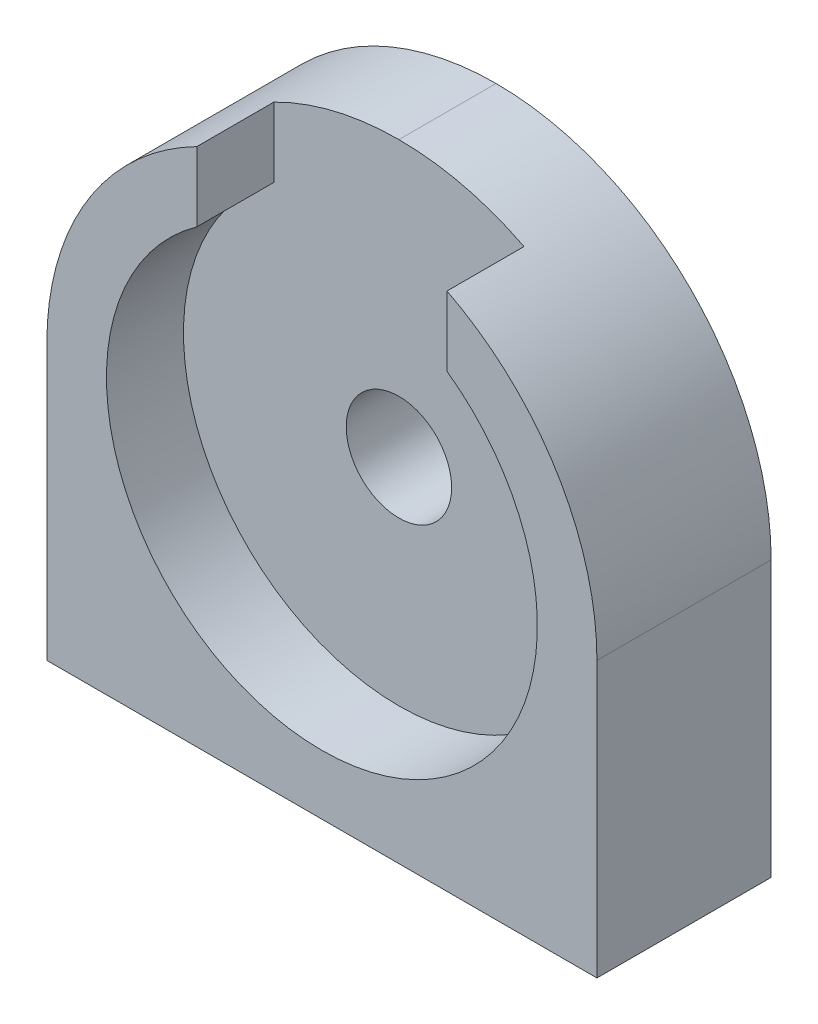
SolidWorks part; units mm, degrees
ref_plane "Front Plane" through (0, 0, 0) normal (0, 0, 1) x (1, 0, 0)
ref_plane "Top Plane" through (0, 0, 0) normal (0, 1, 0) x (1, 0, 0)
ref_plane "Right Plane" through (0, 0, 0) normal (1, 0, 0) x (0, 0, -1)
sketch "Sketch1" plane through (0, 0, 0) normal (0, 0, 1) x (1, 0, 0)
  line L1 (0, 0) -> (15.24, 0)
  line L2 (0, 0) -> (0, 15.24)
  line L3 (0, 15.24) -> (15.24, 15.24)
  line L4 (15.24, 0) -> (15.24, 15.24)
  dimension "D1" = 15.24
  dimension "D2" = 15.24
extrude "Boss-Extrude1" add sketch "Sketch1" along normal blind 25.146
sketch "Sketch2" plane through (0, 0, 25.146) normal (0, 0, 1) x (1, 0, 0)
  circle A0 centre (7.62, 7.62) radius 5.969
  dimension "D1" = 11.938
extrude "Cut-Extrude1" cut sketch "Sketch2" against normal blind 22.4536
fillet "Fillet1" radius 7.62 2 edges at (15.24, 15.24, 12.573) (0, 15.24, 12.573)
sketch "Sketch3" plane through (0, 0, 25.146) normal (0, 0, 1) x (1, 0, 0)
  line L2 (11.0858, 12.4798) -> (11.0858, 15.6004)
  line L3 (11.0858, 15.6004) -> (4.1542, 15.6004)
  line L4 (4.1542, 12.4798) -> (4.1542, 15.6004)
  arc A0 (11.0858, 12.4798) -> (4.1542, 12.4798) centre (7.62, 7.62) ccw
  point P4 (7.62, 15.6004)
  dimension "D1" = 6.9316
extrude "Cut-Extrude2" cut sketch "Sketch3" against normal up to surface (22.4536 mm away) up to face at (13.589, 7.62, 2.6924)
sketch "Sketch4" plane through (0, 0, 2.6924) normal (0, 0, 1) x (1, 0, 0)
  line L0 (7.62, 1.651) -> (7.62, 14.3193) construction
  line L1 (13.589, 7.62) -> (1.651, 7.62) construction
  circle A0 centre (7.62, 7.62) radius 1.4605
  arc A1 (4.1542, 12.4798) -> (11.0858, 12.4798) centre (7.62, 7.62) ccw construction
  dimension "D1" = 2.921
extrude "Cut-Extrude3" cut sketch "Sketch4" against normal through all
sketch "Sketch6" plane through (0, 0, 25.146) normal (0, 0, 1) x (1, 0, 0)
  line L1 (0, 0) -> (16.3747, 0)
  line L2 (0, 0) -> (0, 17.1095)
  line L3 (0, 17.1095) -> (16.3747, 17.1095)
  line L4 (16.3747, 0) -> (16.3747, 17.1095)
extrude "Cut-Extrude5" cut sketch "Sketch6" against normal blind 20.32
sketch "Sketch5" plane through (0, 0, 25.146) normal (0, 0, 1) x (1, 0, 0)
  line L1 (0, 0) -> (2.54, 0)
  line L2 (0, 0) -> (0, 2.54)
  line L3 (0, 2.54) -> (2.54, 2.54)
  line L4 (2.54, 0) -> (2.54, 2.54)
  line L5 (15.24, 0) -> (12.7, 0)
  line L6 (15.24, 0) -> (15.24, 2.54)
  line L7 (15.24, 2.54) -> (12.7, 2.54)
  line L8 (12.7, 0) -> (12.7, 2.54)
  dimension "D1" = 2.54
  dimension "D2" = 2.54
  dimension "D3" = 2.54
  dimension "D4" = 2.54
extrude "Cut-Extrude4" cut sketch "Sketch5" against normal blind 6.35
